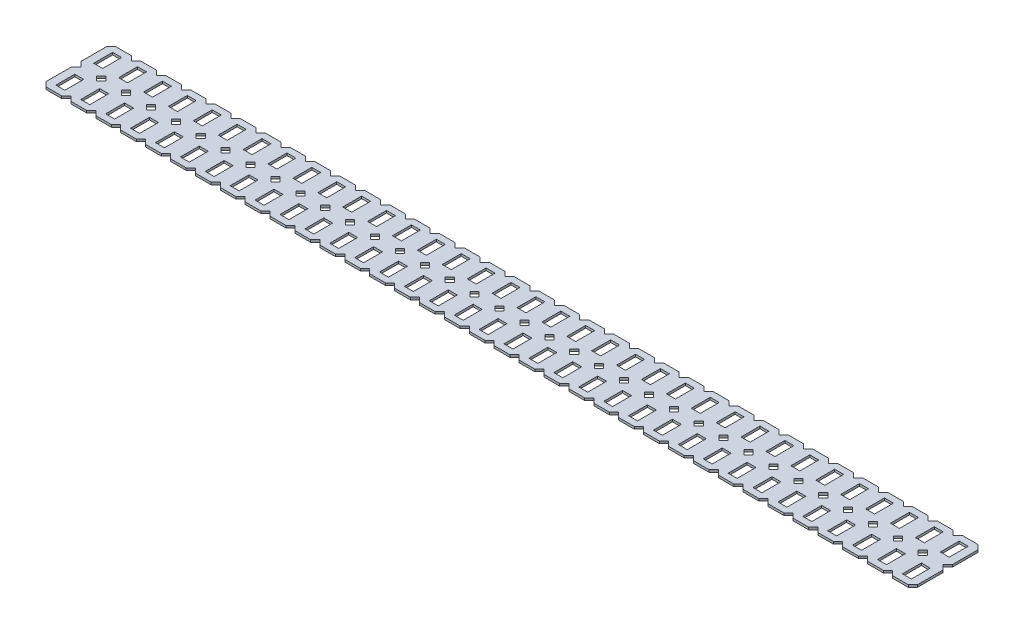
SolidWorks part; units mm, degrees
material "AISI 1020 Steel, Cold Rolled"
ref_plane "Front Plane" through (0, 0, 0) normal (0, 0, 1) x (1, 0, 0)
ref_plane "Top Plane" through (0, 0, 0) normal (0, 1, 0) x (1, 0, 0)
ref_plane "Right Plane" through (0, 0, 0) normal (1, 0, 0) x (0, 0, -1)
sketch "Sketch2" plane through (0, 0, 0) normal (0, 1, 0) x (1, 0, 0)
  line L1 (0, 0) -> (444.5, 0)
  line L2 (0, 0) -> (0, 35.56)
  line L3 (0, 35.56) -> (444.5, 35.56)
  line L4 (444.5, 0) -> (444.5, 35.56)
  dimension "D1" = 444.5
  dimension "D2" = 35.56
extrude "Boss-Extrude1" add sketch "Sketch2" along normal blind 1.1684
sketch "Sketch3" plane through (0, 1.1684, 0) normal (0, 1, 0) x (1, 0, 0)
  line L0 (0, 35.56) -> (0, 0) construction
  line L1 (4.064, 32.258) -> (8.636, 32.258)
  line L2 (4.064, 32.258) -> (4.064, 22.606)
  line L3 (4.064, 22.606) -> (8.636, 22.606)
  line L4 (8.636, 32.258) -> (8.636, 22.606)
  line L5 (4.064, 3.302) -> (8.636, 3.302)
  line L6 (4.064, 3.302) -> (4.064, 12.954)
  line L7 (4.064, 12.954) -> (8.636, 12.954)
  line L8 (8.636, 3.302) -> (8.636, 12.954)
  line L9 (0, 0) -> (444.5, 0) construction
  line L10 (444.5, 35.56) -> (0, 35.56) construction
  dimension "D1" = 9.652
  dimension "D2" = 9.652
  dimension "D3" = 4.572
  dimension "D4" = 4.572
  dimension "D5" = 4.064
  dimension "D6" = 4.064
  dimension "D7" = 3.302
  dimension "D8" = 3.302
extrude "Cut-Extrude1" cut sketch "Sketch3" against normal through all
pattern_linear "LPattern1" count 35 spacing 12.7 along (1, 0, 0) of "Cut-Extrude1"
sketch "Sketch4" plane through (0, 1.1684, 0) normal (0, 1, 0) x (1, 0, 0)
  line L0 (0, 2.3349) -> (2.3349, 0)
  line L1 (0, 35.56) -> (0, 0) construction
  line L2 (0, 0) -> (444.5, 0) construction
  line L3 (0, 2.3349) -> (-2.3349, 0)
  line L4 (-2.3349, 0) -> (0, -2.3349)
  line L5 (0, -2.3349) -> (2.3349, 0)
  dimension "D1" = 3.302
  dimension "D2" = 45
  dimension "D3" = 90
extrude "Cut-Extrude2" cut sketch "Sketch4" against normal through all
pattern_linear "LPattern2" count 36 spacing 12.7 along (1, 0, 0) count 3 spacing 17.78 along (0, 0, -1) of "Cut-Extrude2"
